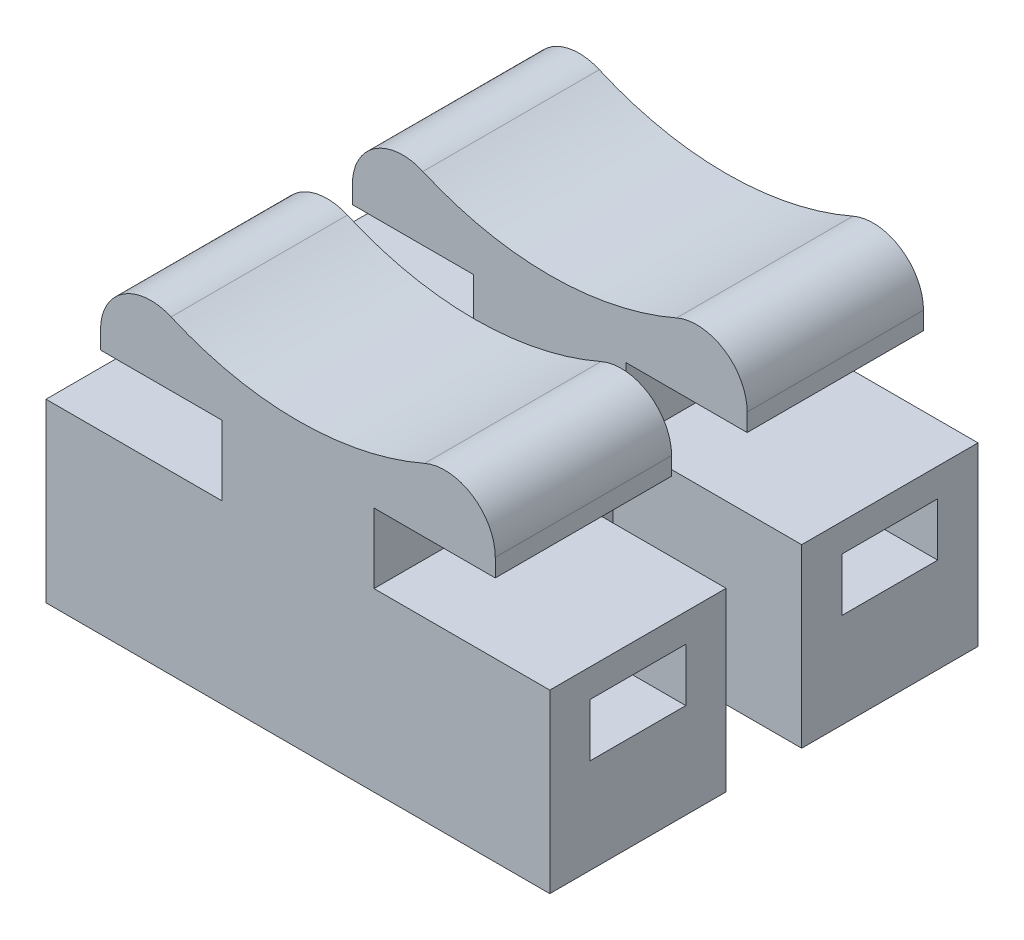
SolidWorks part; units mm, degrees
ref_plane "前视" through (0, 0, 0) normal (0, 0, 1) x (1, 0, 0)
ref_plane "上视" through (0, 0, 0) normal (0, 1, 0) x (1, 0, 0)
ref_plane "右视" through (0, 0, 0) normal (1, 0, 0) x (0, 0, -1)
sketch "草图1" plane through (0, 0, 0) normal (1, 0, 0) x (0, 0, -1)
  line L0 (0, 30.3883) -> (0, -26.2517) construction
  line L1 (-43.0955, 0) -> (39.3578, 0) construction
  line L2 (-5, 14.0646) -> (-5, -6.7193) construction
  line L3 (-1.5, 0) -> (-8.5, 0)
  line L4 (-1.5, 0) -> (-1.5, 7)
  line L5 (-1.5, 7) -> (-8.5, 7)
  line L6 (-8.5, 0) -> (-8.5, 7)
  line L7 (-6.9001, 5.8767) -> (-3.0999, 5.8767)
  line L8 (-6.9001, 5.8767) -> (-6.9001, 3.7671)
  line L9 (-6.9001, 3.7671) -> (-3.0999, 3.7671)
  line L10 (-3.0999, 5.8767) -> (-3.0999, 3.7671)
  line L11 (-10.231, 3.5) -> (10.9268, 3.5) construction
  line L12 (5, 14.0646) -> (5, -6.7193) construction
  line L13 (3.0999, 5.8767) -> (3.0999, 3.7671)
  line L14 (6.9001, 3.7671) -> (3.0999, 3.7671)
  line L15 (6.9001, 5.8767) -> (6.9001, 3.7671)
  line L16 (6.9001, 5.8767) -> (3.0999, 5.8767)
  line L17 (8.5, 0) -> (8.5, 7)
  line L18 (1.5, 7) -> (8.5, 7)
  line L19 (1.5, 0) -> (1.5, 7)
  line L20 (1.5, 0) -> (8.5, 0)
  dimension "D1" = 7
  dimension "D2" = 7
  dimension "D3" = 17
extrude "凸台-拉伸1" add sketch "草图1" along normal blind 10 and the other way blind 10
sketch "草图2" plane through (0, 7, 0) normal (0, 1, 0) x (1, 0, 0)
  line L0 (-10, 1.5) -> (10, 1.5) construction
  line L1 (-2.5, 1.5) -> (2.5, 1.5)
  line L2 (-2.5, 1.5) -> (-2.5, -1.5)
  line L3 (-2.5, -1.5) -> (2.5, -1.5)
  line L4 (2.5, 1.5) -> (2.5, -1.5)
  line L5 (-10, -1.5) -> (10, -1.5) construction
  line L6 (0, 5.5555) -> (0, -5.1438) construction
  line L7 (-5.0141, 0) -> (5.233, 0) construction
  circle A0 centre (0, 0) radius 0.977
  dimension "D1" = 5
extrude "凸台-拉伸2" add sketch "草图2" against normal up to surface (7 mm away) up to face at (0, 0, -5)
sketch "草图3" plane through (0, 0, 8.5) normal (0, 0, 1) x (1, 0, 0)
  line L0 (0, -1.9793) -> (0, 13.5811) construction
  line L1 (-10, 0) -> (10, 0) construction
  line L2 (-7.8357, 14) -> (-7.8357, 9.7722)
  line L3 (-7.8357, 9.7722) -> (-3.0209, 9.7722)
  line L4 (-3.0209, 9.7722) -> (-3.0209, 7)
  line L5 (-10, 7) -> (10, 7) construction
  line L6 (-3.0209, 7) -> (3.0209, 7)
  line L7 (3.0209, 9.7722) -> (3.0209, 7)
  line L8 (7.8357, 9.7722) -> (3.0209, 9.7722)
  line L9 (7.8357, 14) -> (7.8357, 9.7722)
  arc A0 (-7.8357, 14) -> (7.8357, 14) centre (0, 23.8357) ccw
  point P15 (0, 7)
  dimension "D1" = 14
extrude "凸台-拉伸3" add sketch "草图3" against normal up to surface (17 mm away) up to face at (0, 3.5, -8.5)
fillet "圆角1" radius 2 2 edges at (7.8357, 14, 0) (-7.8357, 14, 0)
sketch "草图4" plane through (0, 7, 0) normal (0, 1, 0) x (1, 0, 0)
  line L1 (-10, 1.5) -> (10, 1.5)
  line L2 (-10, 1.5) -> (-10, -1.5)
  line L3 (-10, -1.5) -> (10, -1.5)
  line L4 (10, 1.5) -> (10, -1.5)
extrude "切除-拉伸2" cut sketch "草图4" along normal blind 20
